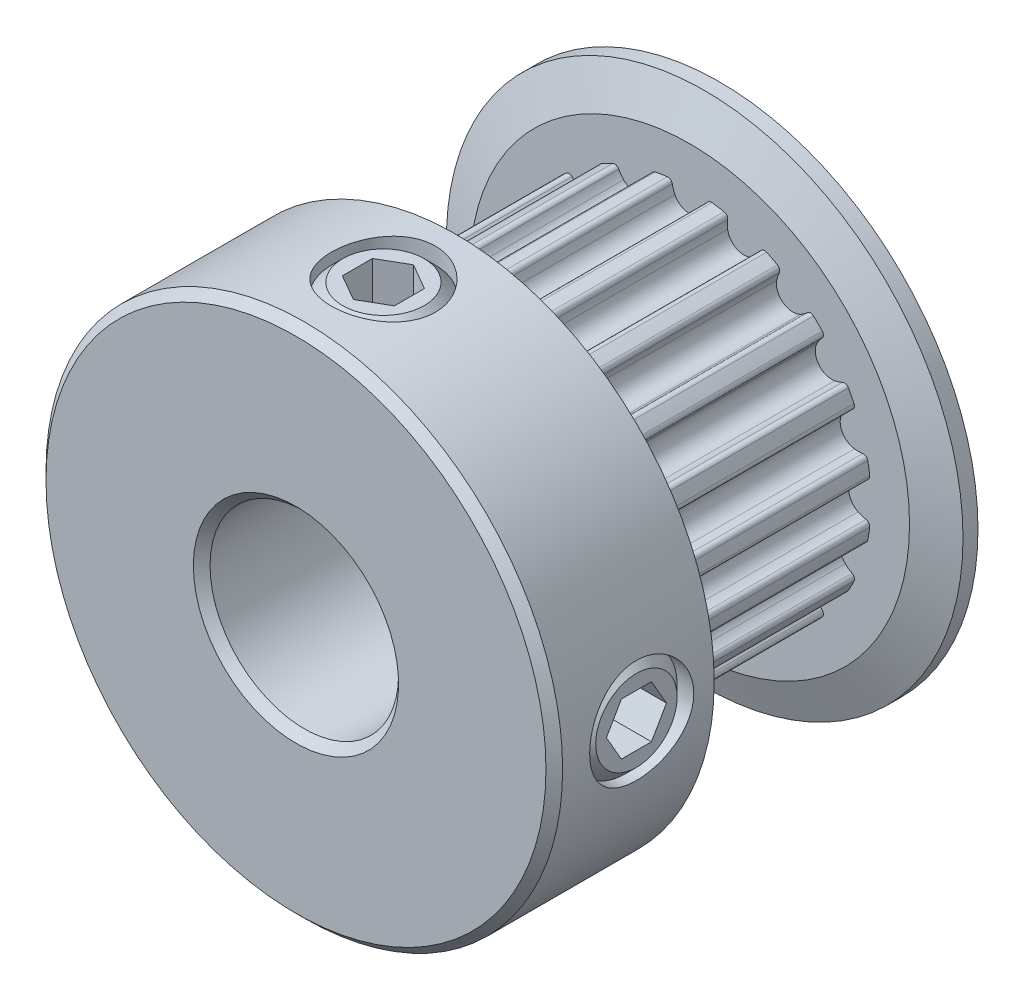
SolidWorks part; units mm, degrees
ref_plane "Front Plane" through (0, 0, 0) normal (0, 0, 1) x (1, 0, 0)
ref_plane "Top Plane" through (0, 0, 0) normal (0, 1, 0) x (1, 0, 0)
ref_plane "Right Plane" through (0, 0, 0) normal (1, 0, 0) x (0, 0, -1)
sketch "Sketch1" plane through (0, 0, 0) normal (0, 0, 1) x (1, 0, 0)
  line L1 (-1.7499, 5.3585) -> (1.7499, 5.3585) construction
  line L4 (0, 0) -> (0, 5.3585) construction
  line L5 (0, 5.3585) -> (0, 11.2119) construction
  line L6 (0, 6.3625) -> (1.9751, 6.0482) construction
  line L7 (1.9751, 6.0482) -> (2.6648, 5.8229) construction
  line L8 (1.9751, 6.0482) -> (1.7499, 5.3585) construction
  line L9 (-1.9751, 6.0482) -> (-1.7499, 5.3585) construction
  line L10 (-1.8963, 5.8067) -> (-2.841, 8.6995)
  line L11 (-2.841, 8.6995) -> (2.841, 8.6995)
  line L12 (2.841, 8.6995) -> (1.8963, 5.8067)
  circle A0 centre (0, 0) radius 6.3625 construction
  circle A1 centre (0, 0) radius 8.6995 construction
  circle A2 centre (0, 0) radius 6.1085 construction
  arc A3 (-0.4989, 5.6703) -> (0.4989, 5.6703) centre (0, 5.9135) ccw
  arc A4 (-0.4989, 5.6703) -> (-0.5855, 5.9387) centre (0.4, 6.1085) cw
  arc A5 (-1.8963, 5.8067) -> (-0.7518, 6.0621) centre (0, 0) cw
  arc A6 (-0.5855, 5.9387) -> (-0.7518, 6.0621) centre (-0.7333, 5.9132) ccw
  arc A7 (1.8963, 5.8067) -> (0.7518, 6.0621) centre (0, 0) ccw
  arc A8 (0.5855, 5.9387) -> (0.7518, 6.0621) centre (0.7333, 5.9132) cw
  arc A9 (0.4989, 5.6703) -> (0.5855, 5.9387) centre (-0.4, 6.1085) ccw
  point P6 (0, 20.9083)
  point P11 (0, 6.3625)
  point P13 (0, 8.6995)
  point P14 (0, 6.1085)
  dimension "D1" = 9.6964
  dimension "D2" = 4.8494
sketch "Sketch2" plane through (0, 0, 0) normal (1, 0, 0) x (0, 0, -1)
  line L0 (-7.135, 3.175) -> (7.135, 3.175)
  line L1 (-7.135, 3.175) -> (-7.135, 8.6995)
  line L2 (-1.75, 8.6995) -> (-7.135, 8.6995)
  line L3 (-2.255, 3.175) -> (-2.255, 8.6995) construction
  line L4 (-2.255, 8.6995) -> (-1.245, 8.6995) construction
  line L5 (-1.245, 8.6995) -> (-1.245, 6.1085) construction
  line L6 (-1.245, 6.1085) -> (6.125, 6.1085)
  line L7 (6.125, 6.1085) -> (6.125, 8.6995) construction
  line L8 (6.125, 8.6995) -> (7.135, 8.6995) construction
  line L9 (7.135, 8.6995) -> (7.135, 3.175)
  line L10 (-7.135, 0) -> (7.135, 0) construction
  line L11 (6.63, 8.6995) -> (6.125, 7.404)
  line L12 (-1.245, 7.404) -> (-1.75, 8.6995)
  line L14 (-1.245, 7.404) -> (-1.245, 6.1085)
  line L15 (6.125, 6.1085) -> (6.125, 7.404)
  line L16 (6.63, 8.6995) -> (7.135, 8.6995)
  arc A0 (-1.245, 7.404) -> (-1.75, 8.6995) centre (-3.1592, 7.404) ccw construction
  arc A1 (6.125, 7.404) -> (6.63, 8.6995) centre (8.0392, 7.404) cw construction
  point P12 (-1.245, 7.404)
  point P14 (-1.75, 8.6995)
  point P20 (6.125, 7.404)
  point P21 (6.63, 8.6995)
  point P25 (6.125, 0)
  point P26 (-1.245, 0)
  dimension "OA" = 14.27
  dimension "Bore" = 6.35
  dimension "Outside Width" = 8.38
  dimension "Inside Width" = 7.37
revolve "Revolve1" add sketch "Sketch2" angle 360 mid plane about L10
sketch "Sketch3" plane through (0, 0, 0) normal (0, 0, 1) x (1, 0, 0)
  line L6 (2.841, 8.6995) -> (-2.841, 8.6995)
  line L7 (1.8963, 5.8067) -> (2.841, 8.6995)
  line L8 (-2.841, 8.6995) -> (-1.8963, 5.8067)
  line L9 (2.841, 8.6995) -> (-2.841, 8.6995)
  line L10 (1.8963, 5.8067) -> (2.841, 8.6995)
  line L11 (-2.841, 8.6995) -> (-1.8963, 5.8067)
  arc A8 (1.8963, 5.8067) -> (0.7518, 6.0621) centre (0, 0) ccw
  arc A9 (0.7518, 6.0621) -> (0.5855, 5.9387) centre (0.7333, 5.9132) ccw
  arc A10 (0.4989, 5.6703) -> (0.5855, 5.9387) centre (-0.4, 6.1085) ccw
  arc A11 (-0.4989, 5.6703) -> (0.4989, 5.6703) centre (0, 5.9135) ccw
  arc A12 (-0.5855, 5.9387) -> (-0.4989, 5.6703) centre (0.4, 6.1085) ccw
  arc A13 (-0.5855, 5.9387) -> (-0.7518, 6.0621) centre (-0.7333, 5.9132) ccw
  arc A14 (-0.7518, 6.0621) -> (-1.8963, 5.8067) centre (0, 0) ccw
  arc A15 (1.8963, 5.8067) -> (0.7518, 6.0621) centre (0, 0) ccw
  arc A16 (0.7518, 6.0621) -> (0.5855, 5.9387) centre (0.7333, 5.9132) ccw
  arc A17 (0.4989, 5.6703) -> (0.5855, 5.9387) centre (-0.4, 6.1085) ccw
  arc A18 (-0.4989, 5.6703) -> (0.4989, 5.6703) centre (0, 5.9135) ccw
  arc A19 (-0.5855, 5.9387) -> (-0.4989, 5.6703) centre (0.4, 6.1085) ccw
  arc A20 (-0.5855, 5.9387) -> (-0.7518, 6.0621) centre (-0.7333, 5.9132) ccw
  arc A21 (-0.7518, 6.0621) -> (-1.8963, 5.8067) centre (0, 0) ccw
  dimension "D1" = 0
extrude "Cut-Extrude1" cut sketch "Sketch3" against normal up to vertex (6.125 mm away) from vertex up to point (0, 6.1085, -6.125) starting at point (0, 6.1085, 1.245)
pattern_circular "CirPattern1" count 20 over 360 about axis through (0, 0, 7.135) along (0, 0, 1) of "Cut-Extrude1"
sketch "Sketch4" plane through (0, 0, 0) normal (1, 0, 0) x (0, -1, 0)
  line L0 (0, -1.245) -> (0, -7.135) construction
  line L1 (-3.175, -7.135) -> (3.175, -7.135) construction
  line L2 (7.404, -1.245) -> (-7.404, -1.245) construction
  circle A0 centre (0, -4.19) radius 1.7526
extrude "Cut-Extrude2" cut sketch "Sketch4" along normal through all
ref_plane "Plane1" through (0, 0, 4.19) normal (0, 0, 1) x (1, 0, 0)
sketch "Sketch5" plane through (0, 0, 4.19) normal (0, 0, 1) x (1, 0, 0)
  line L0 (0, 0) -> (0, 8.6995) construction
  line L1 (3.175, -1.3716) -> (3.175, 0)
  line L2 (3.556, -1.7526) -> (8.1401, -1.7526)
  line L3 (3.175, 0) -> (8.6995, 0) construction
  line L4 (3.175, 0) -> (8.5211, 0)
  line L5 (8.5211, 0) -> (8.5211, -1.3716)
  line L6 (3.556, -1.7526) -> (3.175, -1.3716)
  line L7 (8.5211, -1.3716) -> (8.1401, -1.7526)
  circle A0 centre (0, 0) radius 8.6995 construction
  circle A1 centre (0, 0) radius 3.175 construction
  point P2 (3.175, -1.7526)
  point P11 (8.5211, -1.7526)
revolve "Revolve2" add sketch "Sketch5" angle 360 mid plane about L4
sketch "Sketch6" plane through (8.5211, 5.3841, 0) normal (-1, 0, 0) x (0, -1, 0)
  line L1 (5.3841, 5.2019) -> (4.5078, 4.6959)
  line L2 (4.5078, 4.6959) -> (4.5078, 3.6841)
  line L3 (4.5078, 3.6841) -> (5.3841, 3.1781)
  line L4 (5.3841, 3.1781) -> (6.2604, 3.6841)
  line L5 (6.2604, 3.6841) -> (6.2604, 4.6959)
  line L6 (6.2604, 4.6959) -> (5.3841, 5.2019)
  circle A0 centre (5.3841, 4.19) radius 0.8763 construction
  dimension "D1" = 1.7526
extrude "Cut-Extrude3" cut sketch "Sketch6" along normal blind 1.3144
pattern_circular "CirPattern3" count 2 over 90 about axis through (0, 0, 7.135) along (0, 0, 1) of "Cut-Extrude2", "Revolve2", "Cut-Extrude3"
chamfer "Chamfer1" distance 0.2807 angle 45 2 edges at (3.175, 0, 7.135) (8.6995, 0, 7.135)
ref_axis "Center Axis 1" through (0, 0, -7.135) along (0, 0, 1)
ref_plane "Contact Plane 1" through (0, 0, 7.135) normal (0, 0, 1) x (1, 0, 0)
ref_plane "Contact Plane 2" through (0, 0, -7.135) normal (0, 0, -1) x (-1, 0, 0)
equation "\"D2@Sketch1\"= \"D1@Sketch1\" / 2"
equation "\"D1@Sketch6\" = \"Set Screw@Sketch4\" / 2"
equation "\"D1@Cut-Extrude3\" = \"D1@Sketch6\"*.75"
